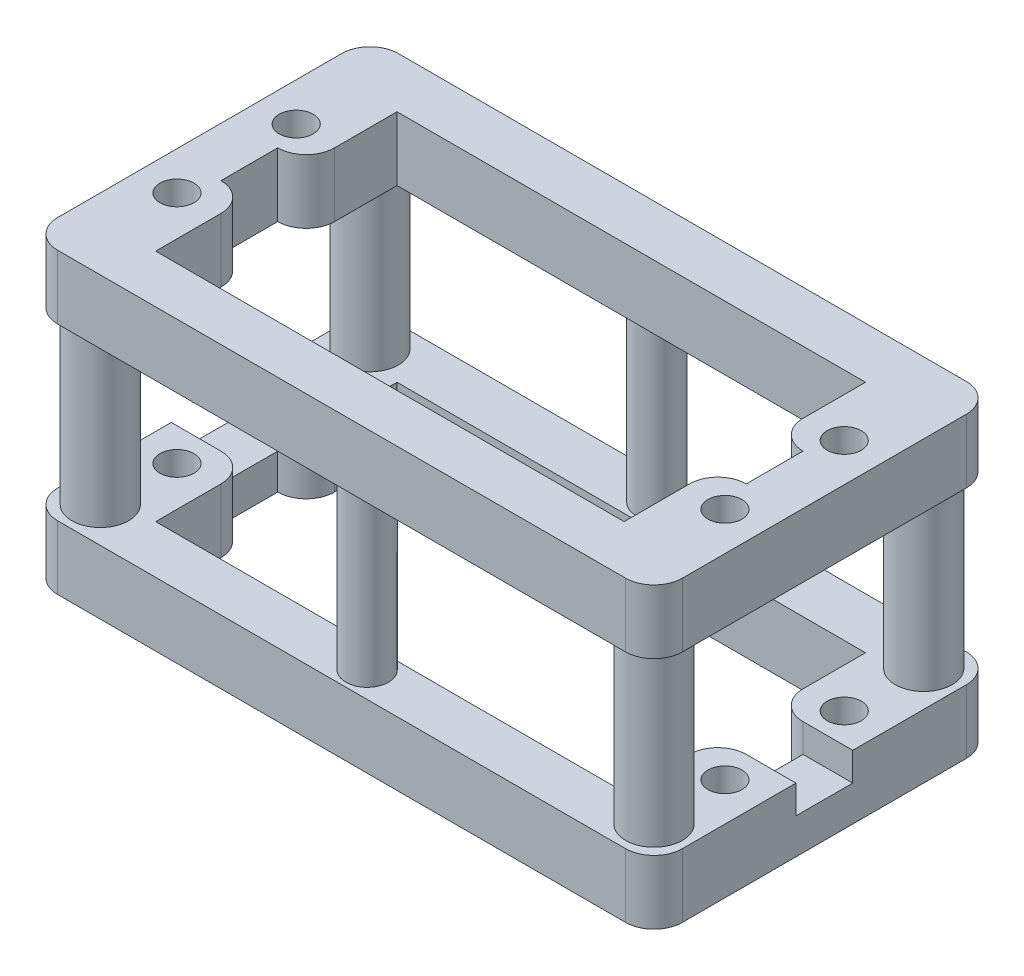
SolidWorks part; units mm, degrees
ref_plane "Front Plane" through (0, 0, 0) normal (0, 0, 1) x (1, 0, 0)
ref_plane "Top Plane" through (0, 0, 0) normal (0, 1, 0) x (1, 0, 0)
ref_plane "Right Plane" through (0, 0, 0) normal (1, 0, 0) x (0, 0, -1)
sketch "Sketch1" plane through (0, 0, 0) normal (0, 1, 0) x (1, 0, 0)
  line L1 (-27.94, -15.24) -> (27.94, -15.24)
  line L2 (-27.94, -15.24) -> (-27.94, 15.24)
  line L3 (-27.94, 15.24) -> (27.94, 15.24)
  line L4 (27.94, -15.24) -> (27.94, 15.24)
  line L5 (0, 15.24) -> (0, -15.24) construction
  line L6 (-27.94, 0) -> (27.94, 0) construction
  point P0 (0, 0)
  dimension "D1" = 55.88
  dimension "D2" = 30.48
extrude "Boss-Extrude1" add sketch "Sketch1" along normal mid plane 26.67 contours L1 L4 L3 L2
sketch "Sketch2" plane through (0, 13.335, 0) normal (0, 1, 0) x (1, 0, 0)
  line L0 (-20.955, 2.54) -> (-20.955, -2.54) construction
  line L1 (-20.955, -10.922) -> (20.955, -10.922)
  line L2 (-20.955, -10.922) -> (-20.955, -2.54)
  line L3 (-20.955, 10.668) -> (20.955, 10.668)
  line L4 (20.955, -10.922) -> (20.955, -2.54)
  line L5 (0, 10.668) -> (0, -10.922) construction
  line L6 (-20.955, 0) -> (20.955, 0) construction
  line L7 (-20.955, 2.54) -> (-23.495, 2.54)
  line L8 (-23.495, 2.54) -> (-23.495, -2.54)
  line L9 (-23.495, -2.54) -> (-20.955, -2.54)
  line L10 (-20.955, 2.54) -> (-20.955, 10.668)
  line L11 (23.495, -2.54) -> (20.955, -2.54)
  line L12 (23.495, 2.54) -> (23.495, -2.54)
  line L13 (20.955, 2.54) -> (23.495, 2.54)
  line L14 (20.955, 2.54) -> (20.955, 10.668)
  line L15 (-27.94, 15.24) -> (27.94, 15.24) construction
  point P0 (0, 0)
  point P6 (-20.955, 0)
  point P7 (-20.955, 0)
  point P8 (-20.955, 0)
  dimension "D1" = 21.59
  dimension "D2" = 41.91
  dimension "D3" = 5.08
  dimension "D4" = 2.54
  dimension "D5" = 5.08
  dimension "D6" = 4.572
extrude "Cut-Extrude1" cut sketch "Sketch2" against normal blind 26.67
sketch "Sketch3" plane through (0, 0, 15.24) normal (0, 0, 1) x (1, 0, 0)
  line L0 (27.94, 13.335) -> (27.94, -13.335) construction
  line L1 (-27.94, -7.62) -> (27.94, -7.62)
  line L2 (-27.94, -7.62) -> (-27.94, 7.62)
  line L3 (-27.94, 7.62) -> (27.94, 7.62)
  line L4 (27.94, -7.62) -> (27.94, 7.62)
  line L5 (0, 7.62) -> (0, -7.62) construction
  line L6 (-27.94, 0) -> (27.94, 0) construction
  point P0 (0, 0)
  dimension "D1" = 15.24
extrude "Cut-Extrude2" cut sketch "Sketch3" against normal up to surface (30.48 mm away) up to face at (0, 0, -15.24)
sketch "Sketch4" plane through (27.94, 0, 0) normal (1, 0, 0) x (0, 0, -1)
  line L0 (0, -7.62) -> (0, -13.335) construction
  line L1 (15.24, -7.62) -> (-15.24, -7.62) construction
  line L2 (-15.24, -13.335) -> (15.24, -13.335) construction
  line L4 (-12.7, -10.16) -> (12.7, -10.16)
  line L5 (-12.7, -10.16) -> (-12.7, -13.335)
  line L6 (-12.7, -13.335) -> (12.7, -13.335)
  line L7 (12.7, -10.16) -> (12.7, -13.335)
  line L8 (0, -13.335) -> (0, -10.16) construction
  line L9 (-12.7, -11.7475) -> (12.7, -11.7475) construction
  point P6 (0, -11.7475)
  dimension "D1" = 3.175
  dimension "D2" = 25.4
extrude "Boss-Extrude2" [suppressed] add sketch "Sketch4" along normal blind 7.62
sketch "Sketch5" plane through (-27.94, 0, 0) normal (-1, 0, 0) x (0, 0, 1)
  line L0 (0, -7.62) -> (0, -13.335) construction
  line L1 (-15.24, -7.62) -> (15.24, -7.62) construction
  line L2 (15.24, -13.335) -> (-15.24, -13.335) construction
  line L4 (-12.7, -13.335) -> (12.7, -13.335)
  line L5 (-12.7, -13.335) -> (-12.7, -10.16)
  line L6 (-12.7, -10.16) -> (12.7, -10.16)
  line L7 (12.7, -13.335) -> (12.7, -10.16)
  line L8 (0, -10.16) -> (0, -13.335) construction
  line L9 (-12.7, -11.7475) -> (12.7, -11.7475) construction
  point P6 (0, -11.7475)
  dimension "D1" = 3.175
  dimension "D2" = 25.4
extrude "Boss-Extrude3" [suppressed] add sketch "Sketch5" along normal blind 7.62
sketch "Sketch6" plane through (0, -7.62, 0) normal (0, 1, 0) x (1, 0, 0)
  line L0 (-27.94, 15.24) -> (-27.94, -15.24) construction
  line L1 (-27.94, -15.24) -> (27.94, -15.24) construction
  line L2 (27.94, 15.24) -> (27.94, -15.24) construction
  line L3 (-27.94, 15.24) -> (-27.94, -15.24) construction
  line L4 (-27.94, 15.24) -> (27.94, 15.24) construction
  line L5 (27.94, 15.24) -> (27.94, -15.24) construction
  circle A0 centre (-24.765, -12.065) radius 2.54
  circle A1 centre (24.765, -12.065) radius 2.54
  circle A2 centre (-24.765, 12.065) radius 2.54
  circle A3 centre (24.765, 12.065) radius 2.54
  circle A4 centre (0, -12.954) radius 1.905
  circle A5 centre (0, 12.954) radius 1.905
  point P22 (0, -15.24)
  dimension "D3" = 5.08
  dimension "D5" = 5.08
  dimension "D8" = 5.08
  dimension "D9" = 5.08
  dimension "D13" = 3.81
  dimension "D15" = 3.81
  dimension "D1" = 3.175
  dimension "D2" = 3.175
  dimension "D4" = 3.175
  dimension "D6" = 3.175
  dimension "D7" = 3.175
  dimension "D10" = 3.175
  dimension "D11" = 3.175
  dimension "D12" = 2.286
  dimension "D14" = 27.94
  dimension "D16" = 2.286
  dimension "D17" = 27.94
extrude "Boss-Extrude4" add sketch "Sketch6" along normal up to surface (15.24 mm away) up to face at (0, 7.62, 0)
sketch "Sketch7" [suppressed] plane through (0, -7.62, 0) normal (0, 1, 0) x (1, 0, 0)
  line L0 (35.56, 12.7) -> (35.56, -12.7) construction
  line L1 (35.56, -12.7) -> (27.94, -12.7) construction
  line L2 (-35.56, -12.7) -> (-35.56, 12.7) construction
  line L3 (-35.56, 12.7) -> (-27.94, 12.7) construction
  line L5 (35.56, 12.7) -> (27.94, 12.7) construction
  line L6 (-35.56, -12.7) -> (-27.94, -12.7) construction
  circle A0 centre (31.75, -5.08) radius 1.5875
  circle A1 centre (-31.75, 5.08) radius 1.5875
  circle A2 centre (31.75, 5.08) radius 1.5875
  circle A3 centre (-31.75, -5.08) radius 1.5875
  dimension "D1" = 3.175
  dimension "D4" = 3.175
  dimension "D7" = 3.175
  dimension "D12" = 3.175
  dimension "D2" = 3.81
  dimension "D3" = 7.62
  dimension "D5" = 3.81
  dimension "D6" = 7.62
  dimension "D8" = 3.81
  dimension "D9" = 7.62
  dimension "D10" = 7.62
  dimension "D11" = 3.81
  dimension "D13" = 10.16
extrude "Cut-Extrude3" [suppressed] cut sketch "Sketch7" against normal up to surface (5.08 mm away)
fillet "Fillet1" radius 2.54 8 edges at (-27.94, 10.4775, 15.24) (-27.94, 10.4775, -15.24) (27.94, 10.4775, -15.24) (27.94, 10.4775, 15.24) (-27.94, -10.4775, -15.24) (27.94, -10.4775, -15.24) (27.94, -10.4775, 15.24) (-27.94, -10.4775, 15.24)
fillet "Fillet2" radius 2.54 8 edges at (20.955, 10.4775, 2.54) (20.955, 10.4775, -2.54) (-20.955, 10.4775, 2.54) (-20.955, 10.4775, -2.54) (20.955, -10.4775, 2.54) (20.955, -10.4775, -2.54) (-20.955, -10.4775, 2.54) (-20.955, -10.4775, -2.54)
sketch "Sketch8" plane through (0, 13.335, 0) normal (0, 1, 0) x (1, 0, 0)
  line L0 (20.955, 5.08) -> (20.955, 10.668) construction
  line L1 (20.955, -10.922) -> (20.955, -5.08) construction
  line L2 (-20.955, 10.668) -> (-20.955, 5.08) construction
  line L3 (20.955, 10.668) -> (-20.955, 10.668) construction
  line L4 (-20.955, -10.922) -> (20.955, -10.922) construction
  circle A0 centre (-24.511, 5.207) radius 1.524
  circle A1 centre (-24.511, -5.461) radius 1.524
  circle A2 centre (24.511, 5.207) radius 1.524
  circle A3 centre (24.511, -5.461) radius 1.524
  dimension "D1" = 3.048
  dimension "D2" = 3.048
  dimension "D3" = 3.048
  dimension "D4" = 3.048
  dimension "D5" = 3.556
  dimension "D6" = 3.556
  dimension "D7" = 3.556
  dimension "D8" = 5.461
  dimension "D9" = 5.461
  dimension "D10" = 5.461
  dimension "D11" = 49.022
  dimension "D12" = 49.022
  dimension "D13" = 10.668
  dimension "D14" = 10.668
extrude "Cut-Extrude4" cut sketch "Sketch8" against normal up to surface (26.67 mm away) up to face at (0, -13.335, 0.0423)
fillet "Fillet3" [suppressed] radius 5.08
sketch "Sketch9" plane through (0, -7.62, 0) normal (0, 1, 0) x (1, 0, 0)
  line L0 (-27.94, 12.7) -> (-27.94, -12.7) construction
  line L1 (-23.495, -2.54) -> (-27.94, -2.54)
  line L2 (-23.495, -2.54) -> (-23.495, 2.54)
  line L3 (-23.495, 2.54) -> (-27.94, 2.54)
  line L4 (-27.94, -2.54) -> (-27.94, 2.54)
  line L5 (27.94, 12.7) -> (27.94, -12.7) construction
  line L6 (23.495, 2.54) -> (27.94, 2.54)
  line L7 (23.495, 2.54) -> (23.495, -2.54)
  line L8 (23.495, -2.54) -> (27.94, -2.54)
  line L9 (27.94, 2.54) -> (27.94, -2.54)
  dimension "D1" = 4.445
  dimension "D2" = 5.08
  dimension "D3" = 4.445
  dimension "D4" = 5.08
extrude "Cut-Extrude5" cut sketch "Sketch9" against normal blind 2.54
